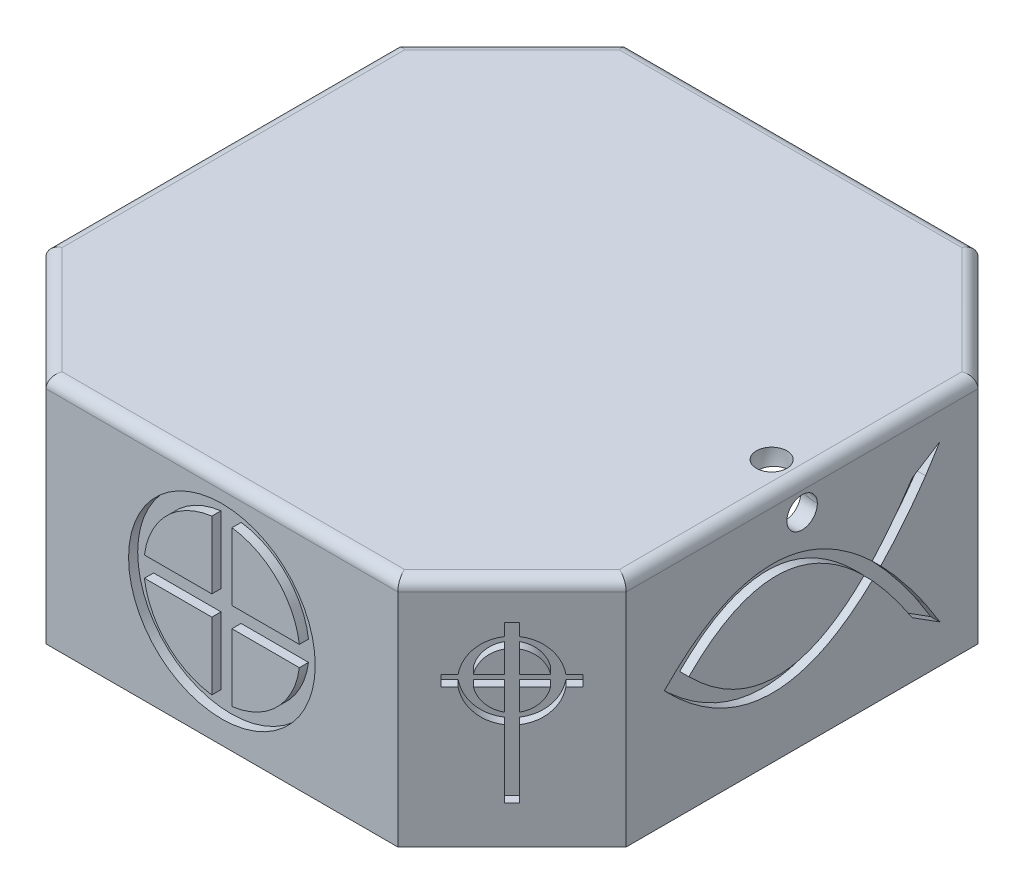
SolidWorks part; units mm, degrees
ref_plane "Front Plane" through (0, 0, 0) normal (0, 0, 1) x (1, 0, 0)
ref_plane "Top Plane" through (0, 0, 0) normal (0, 1, 0) x (1, 0, 0)
ref_plane "Right Plane" through (0, 0, 0) normal (1, 0, 0) x (0, 0, -1)
sketch "Sketch1" plane through (0, 0, 0) normal (0, 1, 0) x (1, 0, 0)
  line L1 (0, 0) -> (38.1, 0)
  line L2 (0, 0) -> (0, 38.1)
  line L3 (0, 38.1) -> (38.1, 38.1)
  line L4 (38.1, 0) -> (38.1, 38.1)
  dimension "D1" = 38.1
extrude "Boss-Extrude1" add sketch "Sketch1" along normal blind 15.2575
sketch "Sketch2" plane through (0, 15.2575, 0) normal (0, 1, 0) x (1, 0, 0)
  line L0 (0, 19.05) -> (38.1, 19.05) construction
  line L1 (0, 38.1) -> (0, 0) construction
  line L2 (38.1, 0) -> (38.1, 38.1) construction
  line L15 (38.1, 30.6) -> (30.6, 38.1)
  line L33 (38.1, 7.5) -> (30.6, 0)
  line L34 (7.5, 0) -> (0, 7.5)
  line L35 (7.5, 38.1) -> (0, 30.6)
  line L36 (38.1, 7.5) -> (38.1, 0)
  line L37 (38.1, 0) -> (30.6, 0)
  line L38 (38.1, 30.6) -> (38.1, 38.1)
  line L39 (38.1, 38.1) -> (30.6, 38.1)
  line L40 (7.5, 38.1) -> (0, 38.1)
  line L41 (0, 38.1) -> (0, 30.6)
  line L42 (0, 7.5) -> (0, 0)
  line L43 (0, 0) -> (7.5, 0)
  line M2 (0, 38.1) -> (0, 0)
  line M3 (0, 0) -> (38.1, 0)
  line M4 (38.1, 0) -> (38.1, 38.1)
  line M5 (38.1, 38.1) -> (0, 38.1)
  dimension "D1" = 7.5
extrude "Cut-Extrude1" cut sketch "Sketch2" against normal through all contours M4 M5 | M5 M2 | M2 M3 | M3 M4 region at (35.6, 15.2575, -35.6) region at (35.6, 15.2575, -2.5) region at (2.5, 15.2575, -35.6) region at (2.5, 15.2575, -2.5)
ref_plane "Plane1" through (30.6, 0, 0) normal (1, 0, 0) x (0, 1, 0)
ref_plane "Plane2" through (0, 0, -19.05) normal (0, 0, 1) x (1, 0, 0)
ref_plane "Plane3" through (19.05, 0, 0) normal (-1, 0, 0) x (0, 0, 1)
sketch "Sketch11" plane through (0, 0, 0) normal (0, -1, 0) x (1, 0, 0)
  line L0 (1.1, -30.1444) -> (7.9556, -37)
  line L1 (7.9556, -37) -> (30.1444, -37)
  line L2 (30.1444, -37) -> (37, -30.1444)
  line L3 (37, -30.1444) -> (37, -7.9556)
  line L4 (37, -7.9556) -> (30.1444, -1.1)
  line L5 (30.1444, -1.1) -> (7.9556, -1.1)
  line L6 (7.9556, -1.1) -> (1.1, -7.9556)
  line L7 (1.1, -7.9556) -> (1.1, -30.1444)
  line L8 (7.5, 0) -> (0, -7.5) construction
  line L10 (1.1, -19.05) -> (0, -19.05) construction
  line L11 (0, -30.6) -> (0, -7.5) construction
  line L14 (19.05, -1.1) -> (19.05, 0) construction
  line L15 (7.5, 0) -> (30.6, 0) construction
  line L18 (37, -19.05) -> (38.1, -19.05) construction
  line L19 (38.1, -7.5) -> (38.1, -30.6) construction
  line L22 (19.05, -37) -> (19.05, -38.1) construction
  line L23 (30.6, -38.1) -> (7.5, -38.1) construction
  dimension "D1" = 1.1
  dimension "D2" = 1.1
extrude "Cut-Extrude5" cut sketch "Sketch11" against normal offset from surface (14.2575 mm away) 1 up to face at (19.05, 15.2575, -19.05)
ref_axis "Axis1" through (19.05, 15.6963, -19.05) along (0, -1, 0)
sketch "Sketch15" plane through (0, 0, -38.1) normal (0, 0, -1) x (-1, 0, 0)
  line L0 (-19.05, 15.2575) -> (-19.05, 0) construction
  line L1 (-30.6, 15.2575) -> (-7.5, 15.2575) construction
  line L2 (-30.6, 0) -> (-7.5, 0) construction
  line L3 (-19.05, 13.7575) -> (-21.7513, 13.7575)
  line L4 (-21.7513, 13.7575) -> (-21.7513, 12.9911)
  line L5 (-21.7513, 12.9911) -> (-19.8974, 12.9911)
  line L6 (-19.8974, 12.9911) -> (-19.8974, 8.4762)
  line L7 (-19.8974, 8.4762) -> (-24.4123, 8.4762)
  line L8 (-24.4123, 8.4762) -> (-24.4123, 10.3301)
  line L9 (-24.4123, 10.3301) -> (-25.1788, 10.3301)
  line L10 (-25.1788, 10.3301) -> (-25.1788, 7.6288)
  line L11 (-22.1549, 8.4762) -> (-22.1549, 10.7336) construction
  line L12 (-22.1549, 10.7336) -> (-19.8974, 10.7336) construction
  line L13 (-22.4049, 11.7205) -> (-21.9049, 11.7205)
  line L14 (-21.9049, 11.7205) -> (-21.9049, 10.9836)
  line L15 (-21.9049, 10.9836) -> (-21.168, 10.9836)
  line L16 (-21.168, 10.9836) -> (-21.168, 10.4836)
  line L17 (-21.9049, 9.7468) -> (-22.4049, 9.7468)
  line L18 (-21.9049, 10.4836) -> (-21.9049, 9.7468)
  line L19 (-21.168, 10.4836) -> (-21.9049, 10.4836)
  line L20 (-23.1417, 10.4836) -> (-23.1417, 10.9836)
  line L21 (-22.4049, 10.4836) -> (-23.1417, 10.4836)
  line L22 (-22.4049, 9.7468) -> (-22.4049, 10.4836)
  line L23 (-22.4049, 11.7205) -> (-21.9049, 11.7205)
  line L24 (-22.4049, 10.9836) -> (-22.4049, 11.7205)
  line L25 (-23.1417, 10.9836) -> (-22.4049, 10.9836)
  line L26 (-19.8974, 8.4762) -> (-19.05, 7.6288) construction
  line L27 (-12.9212, 7.6288) -> (-12.9212, 10.3301)
  line L28 (-12.9212, 10.3301) -> (-13.6877, 10.3301)
  line L29 (-13.6877, 10.3301) -> (-13.6877, 8.4762)
  line L30 (-13.6877, 8.4762) -> (-18.2026, 8.4762)
  line L31 (-18.2026, 8.4762) -> (-18.2026, 12.9911)
  line L32 (-18.2026, 12.9911) -> (-16.3487, 12.9911)
  line L33 (-16.3487, 12.9911) -> (-16.3487, 13.7575)
  line L34 (-16.3487, 13.7575) -> (-19.05, 13.7575)
  line L35 (-14.9583, 10.9836) -> (-14.9583, 10.4836)
  line L36 (-14.9583, 10.4836) -> (-15.6951, 10.4836)
  line L37 (-15.6951, 10.4836) -> (-15.6951, 9.7468)
  line L38 (-15.6951, 9.7468) -> (-16.1951, 9.7468)
  line L39 (-16.932, 10.4836) -> (-16.932, 10.9836)
  line L40 (-16.1951, 10.4836) -> (-16.932, 10.4836)
  line L41 (-16.1951, 9.7468) -> (-16.1951, 10.4836)
  line L42 (-16.1951, 11.7205) -> (-15.6951, 11.7205)
  line L43 (-16.1951, 10.9836) -> (-16.1951, 11.7205)
  line L44 (-16.932, 10.9836) -> (-16.1951, 10.9836)
  line L45 (-14.9583, 10.9836) -> (-14.9583, 10.4836)
  line L46 (-15.6951, 10.9836) -> (-14.9583, 10.9836)
  line L47 (-15.6951, 11.7205) -> (-15.6951, 10.9836)
  line L48 (-18.2026, 10.7336) -> (-15.9451, 10.7336) construction
  line L49 (-15.9451, 10.7336) -> (-15.9451, 8.4762) construction
  line L50 (-19.05, 1.5) -> (-16.3487, 1.5)
  line L51 (-16.3487, 1.5) -> (-16.3487, 2.2665)
  line L52 (-16.3487, 2.2665) -> (-18.2026, 2.2665)
  line L53 (-18.2026, 2.2665) -> (-18.2026, 6.7813)
  line L54 (-18.2026, 6.7813) -> (-13.6877, 6.7813)
  line L55 (-13.6877, 6.7813) -> (-13.6877, 4.9275)
  line L56 (-13.6877, 4.9275) -> (-12.9212, 4.9275)
  line L57 (-12.9212, 4.9275) -> (-12.9212, 7.6288)
  line L58 (-15.6951, 3.537) -> (-16.1951, 3.537)
  line L59 (-16.1951, 3.537) -> (-16.1951, 4.2739)
  line L60 (-16.1951, 4.2739) -> (-16.932, 4.2739)
  line L61 (-16.932, 4.2739) -> (-16.932, 4.7739)
  line L62 (-16.1951, 5.5108) -> (-15.6951, 5.5108)
  line L63 (-16.1951, 4.7739) -> (-16.1951, 5.5108)
  line L64 (-16.932, 4.7739) -> (-16.1951, 4.7739)
  line L65 (-14.9583, 4.7739) -> (-14.9583, 4.2739)
  line L66 (-15.6951, 4.7739) -> (-14.9583, 4.7739)
  line L67 (-15.6951, 5.5108) -> (-15.6951, 4.7739)
  line L68 (-15.6951, 3.537) -> (-16.1951, 3.537)
  line L69 (-15.6951, 4.2739) -> (-15.6951, 3.537)
  line L70 (-14.9583, 4.2739) -> (-15.6951, 4.2739)
  line L71 (-15.9451, 6.7813) -> (-15.9451, 4.5239) construction
  line L72 (-15.9451, 4.5239) -> (-18.2026, 4.5239) construction
  line L73 (-25.1788, 7.6288) -> (-25.1788, 4.9275)
  line L74 (-25.1788, 4.9275) -> (-24.4123, 4.9275)
  line L75 (-24.4123, 4.9275) -> (-24.4123, 6.7813)
  line L76 (-24.4123, 6.7813) -> (-19.8974, 6.7813)
  line L77 (-19.8974, 6.7813) -> (-19.8974, 2.2665)
  line L78 (-19.8974, 2.2665) -> (-21.7513, 2.2665)
  line L79 (-21.7513, 2.2665) -> (-21.7513, 1.5)
  line L80 (-21.7513, 1.5) -> (-19.05, 1.5)
  line L81 (-23.1417, 4.2739) -> (-23.1417, 4.7739)
  line L82 (-23.1417, 4.7739) -> (-22.4049, 4.7739)
  line L83 (-22.4049, 4.7739) -> (-22.4049, 5.5108)
  line L84 (-22.4049, 5.5108) -> (-21.9049, 5.5108)
  line L85 (-21.168, 4.7739) -> (-21.168, 4.2739)
  line L86 (-21.9049, 4.7739) -> (-21.168, 4.7739)
  line L87 (-21.9049, 5.5108) -> (-21.9049, 4.7739)
  line L88 (-21.9049, 3.537) -> (-22.4049, 3.537)
  line L89 (-21.9049, 4.2739) -> (-21.9049, 3.537)
  line L90 (-21.168, 4.2739) -> (-21.9049, 4.2739)
  line L91 (-23.1417, 4.2739) -> (-23.1417, 4.7739)
  line L92 (-22.4049, 4.2739) -> (-23.1417, 4.2739)
  line L93 (-22.4049, 3.537) -> (-22.4049, 4.2739)
  line L94 (-19.8974, 4.5239) -> (-22.1549, 4.5239) construction
  line L95 (-22.1549, 4.5239) -> (-22.1549, 6.7813) construction
  point P24 (-21.168, 10.7336)
  point P25 (-22.1549, 11.7205)
  point P26 (-19.05, 7.6288)
  point P40 (-22.1549, 10.7336)
  point P57 (-15.9451, 9.7468)
  point P58 (-14.9583, 10.7336)
  point P68 (-15.9451, 10.7336)
  point P86 (-16.932, 4.5239)
  point P87 (-15.9451, 3.537)
  point P97 (-15.9451, 4.5239)
  point P115 (-22.1549, 5.5108)
  point P116 (-23.1417, 4.5239)
  point P126 (-22.1549, 4.5239)
  point P127 (-19.05, 7.6288)
  dimension "D1" = 45
  dimension "D3" = 0.5
  dimension "D4" = 1.5
  dimension "D5" = 1.5
  dimension "D2" = 4
extrude "Cut-Extrude9" cut sketch "Sketch15" against normal blind 0.6 contours L79 L80 L50 L51 L52 L53 L54 L55 L56 L57 L27 L28 L29 L30 L31 L32 L33 L34 L3 L4 L5 L6 L7 L8 L9 L10 L73 L74 L75 L76 L77 L78 | L25 L20 L21 L22 L17 L18 L19 L16 L15 L14 L13 L24 | L47 L42 L43 L44 L39 L40 L41 L38 L37 L36 L35 L46 | L70 L65 L66 L67 L62 L63 L64 L61 L60 L59 L58 L69 | L93 L88 L89 L90 L85 L86 L87 L84 L83 L82 L81 L92 region at (19.05, 7.6288, -38.1) region at (22.1549, 10.7336, -38.1) region at (15.9451, 10.7336, -38.1) region at (15.9451, 4.5239, -38.1) region at (22.1549, 4.5239, -38.1)
sketch "Sketch16" plane through (38.1, 0, 0) normal (1, 0, 0) x (0, 0, -1)
  line L3 (30.6, 7.6288) -> (7.5, 7.6288) construction
  line L6 (30.6, 0) -> (30.6, 15.2575) construction
  line L7 (7.5, 0) -> (7.5, 15.2575) construction
  line L8 (26.2863, 3.6462) -> (28.1, 2.5)
  line L9 (28.1, 2.5) -> (27.1575, 3.9759)
  line L10 (28.1, 12.7575) -> (27.1575, 11.2816)
  line L11 (26.2863, 11.6113) -> (28.1, 12.7575)
  line L12 (7.5, 12.7575) -> (30.6, 12.7575) construction
  line L13 (7.5, 15.2575) -> (30.6, 15.2575) construction
  line L14 (28.1, 0) -> (28.1, 15.2575) construction
  line L15 (7.5, 0) -> (30.6, 0) construction
  line L16 (10, 0) -> (10, 15.2575) construction
  spline S0 degree 2 poles (10, 7.6288) (18.5373, 16.4878) (27.1575, 3.9759) knots 0 0 0 1 1 1
  spline S1 degree 2 poles (10, 7.6288) (18.5373, -1.2303) (27.1575, 11.2816) knots 0 0 0 1 1 1
  spline S2 degree 2 poles (11.6123, 7.6288) (18.8837, 14.9283) (26.2863, 3.6462) knots 0 0 0 1 1 1
  spline S3 degree 2 poles (11.6123, 7.6288) (18.8837, 0.3292) (26.2863, 11.6113) knots 0 0 0 1 1 1
  dimension "D1" = 2.5
  dimension "D2" = 2.5
  dimension "D3" = 2.5
extrude "Cut-Extrude10" cut sketch "Sketch16" against normal blind 0.6 contours S3 S2 S0 S1 | S3 S2 S1 S0 | S3 S0 S1 L10 L11 | S1 S2 L8 L9 S0 region at (38.1, 5.1978, -25.7209) region at (38.1, 7.6288, -23.6658) region at (38.1, 4.1218, -16.7193) region at (38.1, 10.0598, -25.7209)
sketch "Sketch17" plane through (0, 0, 0) normal (-1, 0, 0) x (0, 0, 1)
  line L0 (-19.05, 0) -> (-19.05, 15.2575) construction
  line L1 (-19.05, 7.2427) -> (-19.05, 8.0148) construction
  line L2 (-19.3928, 12.7575) -> (-19.3928, 2.5)
  line L4 (-15.7969, 6.3304) -> (-16.1122, 5.7215)
  line L5 (-16.1122, 5.7215) -> (-19.05, 7.2427)
  line L17 (-30.6, 0) -> (-7.5, 0) construction
  line L18 (-30.6, 15.2575) -> (-7.5, 15.2575) construction
  line L19 (-30.6, 2.5) -> (-7.5, 2.5) construction
  line L20 (-30.6, 0) -> (-30.6, 15.2575) construction
  line L21 (-7.5, 0) -> (-7.5, 15.2575) construction
  line L22 (-7.5, 12.7575) -> (-30.6, 12.7575) construction
  line L35 (-22.3031, 8.9271) -> (-19.7956, 7.6288)
  line L36 (-19.7956, 7.6288) -> (-22.3031, 6.3304)
  line L37 (-22.3031, 6.3304) -> (-21.9878, 5.7215)
  line L38 (-21.9878, 5.7215) -> (-19.05, 7.2427)
  line L39 (-22.3031, 8.9271) -> (-21.9878, 9.536)
  line L40 (-21.9878, 9.536) -> (-19.05, 8.0148)
  line L41 (-21.9878, 9.536) -> (-21.9878, 12.7575) construction
  line L49 (-21.9878, 5.7215) -> (-21.9878, 2.5) construction
  line L50 (-18.3044, 7.6288) -> (-15.7969, 6.3304)
  line L51 (-15.7969, 8.9271) -> (-16.1122, 9.536)
  line L52 (-16.1122, 9.536) -> (-19.05, 8.0148)
  line L53 (-15.7969, 8.9271) -> (-18.3044, 7.6288)
  line L54 (-19.3928, 2.5) -> (-18.7072, 2.5)
  line L55 (-18.7072, 2.5) -> (-18.7072, 8.9439)
  line L56 (-18.7072, 9.536) -> (-18.7072, 12.3338)
  circle A0 centre (-19.05, 7.6288) radius 5.2727 construction
  spline S0 degree 3 poles (-19.3928, 12.7575) (-17.2074, 13.5676) (-13.3053, 10.0419) (-18.7072, 8.9439) knots 0 0 0 0 1 1 1 1
  spline S1 degree 3 poles (-18.7072, 12.3338) (-17.4138, 12.2051) (-16.2275, 11.671) (-16.6246, 9.9515) (-18.7072, 9.536) knots 0 0 0 0 0.586633 1 1 1 1
  point P25 (-19.05, 12.7575)
  point P30 (-19.05, 2.5)
  point P59 (-19.05, 2.5)
  dimension "D1" = 2.5
  dimension "D2" = 2.5
extrude "Cut-Extrude13" cut sketch "Sketch17" against normal blind 0.6 contours L40 L39 L35 L36 L37 L38 L2 | L5 L55 L52 L40 L2 L38 | L54 L55 L5 L38 L2 | L55 L5 L4 L50 L53 L51 L52 | S0 L2 L40 L52 L55 L56 S1 region at (0, 11.2264, -16.1043) region at (0, 7.6288, -19.05) region at (0, 7.6288, -19.4408) region at (0, 4.8273, -19.05) region at (0, 8.8216, -17.3876)
sketch "Sketch20" plane through (-15.3, 0, -15.3) normal (-0.7071, 0, -0.7071) x (-0.7071, 0, 0.7071)
  line L0 (-26.9408, 0) -> (-26.9408, 15.2575) construction
  line L1 (-32.2441, 0) -> (-21.6375, 0) construction
  line L2 (-32.2441, 15.2575) -> (-21.6375, 15.2575) construction
  line L3 (-32.2441, 12.7575) -> (-21.6375, 12.7575) construction
  line L4 (-32.2441, 0) -> (-32.2441, 15.2575) construction
  line L5 (-21.6375, 0) -> (-21.6375, 15.2575) construction
  line L6 (-21.6375, 2.5) -> (-32.2441, 2.5) construction
  line L7 (-26.1908, 12.7575) -> (-27.6908, 12.7575)
  line L8 (-27.6908, 12.7575) -> (-27.6908, 10.4176)
  line L9 (-27.6908, 10.4176) -> (-30.0307, 10.4176)
  line L10 (-30.0307, 10.4176) -> (-30.0307, 8.9176)
  line L11 (-30.0307, 8.9176) -> (-27.6908, 8.9176)
  line L12 (-27.6908, 8.9176) -> (-27.6908, 2.5)
  line L13 (-27.6908, 2.5) -> (-26.1908, 2.5)
  line L14 (-26.1908, 12.7575) -> (-26.1908, 10.4176)
  line L15 (-26.1908, 10.4176) -> (-23.8508, 10.4176)
  line L16 (-23.8508, 10.4176) -> (-23.8508, 8.9176)
  line L17 (-23.8508, 8.9176) -> (-26.1908, 8.9176)
  line L18 (-26.1908, 8.9176) -> (-26.1908, 2.5)
  point P23 (-26.9408, 12.7575)
  point P28 (-26.9408, 2.5)
  dimension "D1" = 2.5
  dimension "D2" = 2.5
  dimension "D3" = 1.5
extrude "Cut-Extrude15" cut sketch "Sketch20" against normal blind 0.6
sketch "Sketch21" plane through (3.75, 0, -3.75) normal (-0.7071, 0, 0.7071) x (0.7071, 0, 0.7071)
  line L0 (-5.3033, 7.6288) -> (5.3033, 7.6288) construction
  line L1 (-5.3033, 0) -> (-5.3033, 15.2575) construction
  line L2 (5.3033, 0) -> (5.3033, 15.2575) construction
  line L3 (0, 0) -> (0, 15.2575) construction
  line L4 (5.3033, 0) -> (-5.3033, 0) construction
  line L5 (5.3033, 15.2575) -> (-5.3033, 15.2575) construction
  line L6 (0, 7.6288) -> (-6.9275, 7.6288) construction
  line L7 (0, 7.6288) -> (0, 14.5563) construction
  circle A0 centre (-6.9275, 7.6288) radius 6.5854
  circle A3 centre (-6.9275, 7.6288) radius 3.3813
  circle A4 centre (0, 14.5563) radius 3.3813
  circle A5 centre (0, 14.5563) radius 6.5854
  circle A6 centre (6.9275, 7.6288) radius 3.3813
  circle A7 centre (6.9275, 7.6288) radius 6.5854
  circle A8 centre (0, 0.7012) radius 3.3813
  circle A9 centre (0, 0.7012) radius 6.5854
  point P29 (0, 7.6288)
  dimension "D1" = 4
extrude "Cut-Extrude16" cut sketch "Sketch21" against normal blind 0.6 contours A9 A0 A5 A3 | A9 A7 A5 A0 | A9 A6 A5 A7 | A7 A9 A0 A8 | A7 A4 A0 A5 region at (2.0374, 7.6288, -5.4626) region at (3.75, 7.6288, -3.75) region at (3.75, 10.0508, -3.75) region at (3.75, 5.2068, -3.75) region at (5.4626, 7.6288, -2.0374)
sketch "Sketch22" plane through (15.3, 0, 15.3) normal (0.7071, 0, 0.7071) x (0.7071, 0, -0.7071)
  line L0 (26.9408, 0) -> (26.9408, 15.2575) construction
  line L1 (32.2441, 0) -> (21.6375, 0) construction
  line L2 (32.2441, 15.2575) -> (21.6375, 15.2575) construction
  line L3 (21.6375, 7.6288) -> (32.2441, 7.6288) construction
  line L4 (21.6375, 0) -> (21.6375, 15.2575) construction
  line L5 (32.2441, 0) -> (32.2441, 15.2575) construction
  line L6 (27.2903, 12.7575) -> (26.5912, 12.7575)
  line L7 (26.5912, 12.7575) -> (26.5912, 9.8124)
  line L8 (26.5912, 9.8124) -> (23.6461, 9.8124)
  line L9 (23.6461, 9.8124) -> (23.6461, 9.1133)
  line L10 (23.6461, 9.1133) -> (26.5912, 9.1133)
  line L11 (26.5912, 9.1133) -> (26.5912, 2.5)
  line L12 (26.5912, 2.5) -> (27.2903, 2.5)
  line L13 (27.2903, 12.7575) -> (27.2903, 9.8124)
  line L14 (30.2355, 9.1133) -> (27.2903, 9.1133)
  line L15 (30.2355, 9.8124) -> (30.2355, 9.1133)
  line L16 (27.2903, 9.8124) -> (30.2355, 9.8124)
  line L17 (27.2903, 9.1133) -> (27.2903, 2.5)
  line L18 (27.2903, 9.1133) -> (26.5912, 9.8124) construction
  line L19 (26.9408, 11.2916) -> (26.9408, 11.9907) construction
  line L20 (32.2441, 12.7575) -> (21.6375, 12.7575) construction
  circle A0 centre (26.9408, 9.4628) radius 2.5279
  circle A1 centre (26.9408, 9.4628) radius 1.8288
  point P21 (26.9408, 12.7575)
  point P26 (26.9408, 2.5)
  dimension "D1" = 2.5
  dimension "D2" = 2.5
extrude "Cut-Extrude17" cut sketch "Sketch22" against normal blind 0.6 contours A0 L11 L12 L17 | A1 L10 A0 L11 | A1 L17 A0 L14 | A1 L14 A0 L16 | A1 L16 A0 L13 | A0 L14 L15 L16 | L13 A1 L7 L8 L10 L11 L17 L14 L16 | A1 L8 A0 L10 | A0 L8 L9 L10 | A1 L7 A0 L8 | A1 L13 A0 L7 | A0 L13 L6 L7 | A1 L11 A0 L17 region at (34.35, 12.3701, -3.75) region at (35.3804, 10.9201, -4.7804) region at (34.35, 11.6315, -3.75) region at (33.3196, 10.9201, -2.7196) region at (34.35, 9.4628, -3.75) region at (35.8835, 9.4628, -5.2835) region at (36.4057, 9.4628, -5.8057) region at (32.2943, 9.4628, -1.6943) region at (32.8165, 9.4628, -2.2165) region at (33.3196, 8.0056, -2.7196) region at (35.3804, 8.0056, -4.7804) region at (34.35, 4.7215, -3.75) region at (34.35, 7.2942, -3.75)
sketch "Sketch23" plane through (34.35, 0, -34.35) normal (0.7071, 0, -0.7071) x (-0.7071, 0, -0.7071)
  line L0 (-5.3033, 12.7575) -> (5.3033, 12.7575) construction
  line L1 (-5.3033, 0) -> (-5.3033, 15.2575) construction
  line L2 (5.3033, 0) -> (5.3033, 15.2575) construction
  line L3 (5.3033, 2.5) -> (-5.3033, 2.5) construction
  line L4 (-5.3033, 15.2575) -> (5.3033, 15.2575) construction
  line L5 (-5.3033, 0) -> (5.3033, 0) construction
  line L6 (0, 12.7575) -> (0, 2.5) construction
  line L7 (0.3566, 12.7575) -> (-0.3566, 12.7575)
  line L8 (-0.3566, 12.7575) -> (-0.3566, 11.8791)
  line L9 (-0.3566, 11.8791) -> (-1.6164, 11.8791)
  line L10 (-1.6164, 11.8791) -> (-1.6164, 11.1659)
  line L11 (-1.6164, 11.1659) -> (-0.3566, 11.1659)
  line L12 (-0.3566, 11.1659) -> (-0.3566, 10.2875)
  line L13 (-0.3566, 10.2875) -> (-2.4075, 10.2875)
  line L14 (-2.4075, 10.2875) -> (-2.4075, 9.5743)
  line L15 (-2.4075, 9.5743) -> (-0.3566, 9.5743)
  line L16 (-0.3566, 9.5743) -> (-0.3566, 8.6959)
  line L17 (-0.3566, 8.6959) -> (-3.1986, 8.6959)
  line L18 (-3.1986, 8.6959) -> (-3.1986, 7.9827)
  line L19 (-3.1986, 7.9827) -> (-0.3566, 7.9827)
  line L20 (-0.3566, 7.9827) -> (-0.3566, 2.5)
  line L21 (-0.3566, 2.5) -> (0.3566, 2.5)
  line L22 (-1.6164, 11.1659) -> (-2.4075, 11.1659) construction
  line L23 (-2.4075, 11.1659) -> (-2.4075, 10.2875) construction
  line L24 (-2.4075, 9.5743) -> (-3.1986, 9.5743) construction
  line L25 (-3.1986, 9.5743) -> (-3.1986, 8.6959) construction
  line L26 (3.1986, 9.5743) -> (3.1986, 8.6959) construction
  line L27 (2.4075, 9.5743) -> (3.1986, 9.5743) construction
  line L28 (2.4075, 11.1659) -> (2.4075, 10.2875) construction
  line L29 (1.6164, 11.1659) -> (2.4075, 11.1659) construction
  line L30 (0.3566, 7.9827) -> (0.3566, 2.5)
  line L31 (3.1986, 7.9827) -> (0.3566, 7.9827)
  line L32 (3.1986, 8.6959) -> (3.1986, 7.9827)
  line L33 (0.3566, 8.6959) -> (3.1986, 8.6959)
  line L34 (0.3566, 9.5743) -> (0.3566, 8.6959)
  line L35 (2.4075, 9.5743) -> (0.3566, 9.5743)
  line L36 (2.4075, 10.2875) -> (2.4075, 9.5743)
  line L37 (0.3566, 10.2875) -> (2.4075, 10.2875)
  line L38 (0.3566, 11.1659) -> (0.3566, 10.2875)
  line L39 (1.6164, 11.1659) -> (0.3566, 11.1659)
  line L40 (1.6164, 11.8791) -> (1.6164, 11.1659)
  line L41 (0.3566, 11.8791) -> (1.6164, 11.8791)
  line L42 (0.3566, 12.7575) -> (0.3566, 11.8791)
  dimension "D1" = 2.5
  dimension "D2" = 2.5
extrude "Cut-Extrude18" cut sketch "Sketch23" against normal blind 0.6
sketch "Sketch24" plane through (0, 0, 0) normal (0, 0, 1) x (1, 0, 0)
  line L0 (19.05, 0) -> (19.05, 15.2575) construction
  line L1 (7.5, 0) -> (30.6, 0) construction
  line L2 (7.5, 15.2575) -> (30.6, 15.2575) construction
  line L3 (7.5, 12.7575) -> (30.6, 12.7575) construction
  line L4 (7.5, 0) -> (7.5, 15.2575) construction
  line L5 (30.6, 0) -> (30.6, 15.2575) construction
  line L6 (16.3487, 13.7575) -> (21.7513, 13.7575) construction
  line L7 (16.3487, 13.7575) -> (21.7513, 13.7575)
  line L8 (13.9639, 8.289) -> (18.3898, 8.289)
  line L9 (18.3898, 8.289) -> (18.3898, 12.7149)
  line L10 (19.7102, 8.289) -> (24.1361, 8.289)
  line L11 (19.7102, 12.7149) -> (19.7102, 8.289)
  line L12 (19.7102, 6.9686) -> (19.7102, 2.5427)
  line L13 (24.1361, 6.9686) -> (19.7102, 6.9686)
  line L14 (18.3898, 6.9686) -> (13.9639, 6.9686)
  line L15 (18.3898, 2.5427) -> (18.3898, 6.9686)
  circle A0 centre (19.05, 7.6288) radius 5.1288
  circle A1 centre (19.05, 7.6288) radius 6.1288
  point P32 (19.05, 7.6288)
  dimension "D2" = 4
  dimension "D1" = 2.5
extrude "Cut-Extrude19" cut sketch "Sketch24" against normal blind 0.6 contours L11 A0 L9 L8 L14 L15 L12 L13 L10 | A1 A0 region at (19.05, 7.6288, 0) region at (14.8389, 3.4176, 0)
sketch "Sketch25" plane through (38.1, 0, 0) normal (1, 0, 0) x (0, 0, -1)
  line L0 (7.9556, 14.2575) -> (30.1444, 14.2575) construction
  line L1 (7.9556, 14.2575) -> (30.1444, 14.2575) construction
  line L2 (19.05, 14.2575) -> (19.05, 13.2575) construction
  circle A0 centre (19.05, 13.2575) radius 1
  point P6 (18.952, 13.3196)
  dimension "D1" = 2
extrude "Cut-Extrude20" cut sketch "Sketch25" against normal up to surface (1.1 mm away) up to face at (37, 7.1288, -19.05)
sketch "Sketch26" plane through (38.1, 0, 0) normal (1, 0, 0) x (0, 0, -1)
  circle A0 centre (19.05, 13.2575) radius 1 construction
  circle A1 centre (19.05, 13.2575) radius 1
revolve "Cut-Revolve1" cut sketch "Sketch26" angle 360 about axis through (38.1, 15.2575, 0) along (0, 0, -1)
fillet "Fillet1" radius 0.75 8 edges at (34.35, 15.2575, -3.75) (38.1, 15.2575, -19.05) (34.35, 15.2575, -34.35) (19.05, 15.2575, -38.1) (3.75, 15.2575, -34.35) (19.05, 15.2575, 0) (3.75, 15.2575, -3.75) (0, 15.2575, -19.05)
